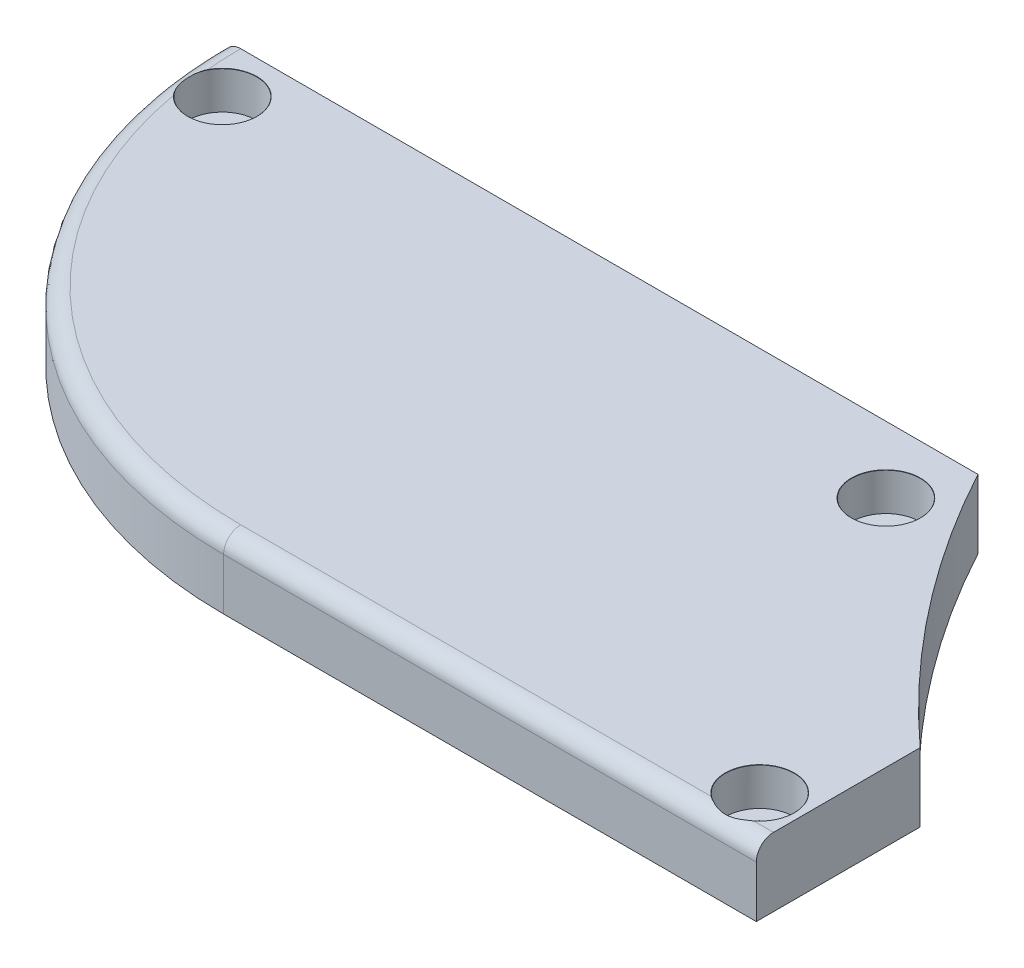
SolidWorks part; units mm, degrees
ref_plane "Front Plane" through (0, 0, 0) normal (0, 0, 1) x (1, 0, 0)
ref_plane "Top Plane" through (0, 0, 0) normal (0, 1, 0) x (1, 0, 0)
ref_plane "Right Plane" through (0, 0, 0) normal (1, 0, 0) x (0, 0, -1)
sketch "Sketch6" plane through (0, 0, 0) normal (0, 1, 0) x (1, 0, 0)
  line L2 (-49.2415, 24.8645) -> (-56.554, 24.8645)
  line L3 (-6.554, -25.1355) -> (55.4701, -25.1355)
  line L4 (55.4701, -25.1355) -> (55.4701, -6.0571)
  line L5 (31.2807, 24.8645) -> (15.2575, 24.8645)
  line L6 (-49.2415, 24.8645) -> (15.2575, 24.8645)
  arc A4 (-56.554, 24.8645) -> (-6.554, -25.1355) centre (-6.554, 24.8645) ccw
  arc A5 (31.2807, 24.8645) -> (55.4701, -6.0571) centre (133.446, 79.8645) ccw
extrude "Boss-Extrude2" add sketch "Sketch6" along normal blind 8 contours L6 L2 A4 L3 L4 A5 L5
sketch "Sketch7" plane through (0, 8, 0) normal (0, 1, 0) x (1, 0, 0)
  circle A0 centre (-52.2739, 21.307) radius 2.025
  circle A1 centre (50.689, -19.9544) radius 2.025
  circle A7 centre (28.2999, 17.1229) radius 2.025
sketch "Sketch11" plane through (0, 8, 0) normal (0, 1, 0) x (1, 0, 0)
  line L0 (50.4701, -8.2436) -> (50.4701, -18.1474)
  line L1 (48.0604, -20.1355) -> (-6.554, -20.1355)
  line L2 (-46.6352, 24.8645) -> (-56.554, 24.8645)
  line L3 (-6.554, -25.1355) -> (55.4701, -25.1355)
  line L4 (55.4701, -25.1355) -> (55.4701, -6.0571)
  line L5 (31.2807, 24.8645) -> (15.2575, 24.8645)
  circle A0 centre (-50.8096, 18.9764) radius 2.025
  arc A1 (48.0604, -20.1355) -> (50.4701, -18.1474) centre (50.0854, -20.1355) ccw
  arc A2 (-50.6388, 15.8351) -> (-6.554, -20.1355) centre (-6.554, 24.8645) ccw
  arc A3 (-56.554, 24.8645) -> (-6.554, -25.1355) centre (-6.554, 24.8645) ccw
  arc A4 (31.2807, 24.8645) -> (55.4701, -6.0571) centre (133.446, 79.8645) ccw
  arc A5 (31.9468, 13.9406) -> (50.4701, -8.2436) centre (133.446, 79.8645) ccw
  parabola Q0 (-50.6388, 15.8351) -> (-46.6352, 24.8645) focus (-49.7568, 20.4276) apex (-47.0818, 18.9898)
  spline S0 degree 3 poles (15.2575, 24.8645) (23.9964, 24.6371) (21.8005, 8.7848) (31.9468, 13.9406) knots 0 0 0 0 1 1 1 1
hole_wizard "CBORE for M4 Hex Socket Head Cap Screw1" positions "Sketch8" profile "Sketch9" counterbore size "M4" standard "ISO"
sketch "Sketch8" plane through (0, 8, 0) normal (0, 1, 0) x (1, 0, 0)
  point P3 (28.2999, 17.1229)
  point P6 (50.689, -19.9544)
  point P14 (-50.8096, 18.9764)
sketch "Sketch9" plane through (28.2999, 8, -17.1229) normal (1, 0, 0) x (0, 0, 1)
  line L0 (0, 0) -> (0, 11.4519)
  line L1 (0, 11.4519) -> (2.25, 10.1)
  line L2 (2.25, 10.1) -> (2.25, 4.4)
  line L3 (2.25, 4.4) -> (4, 4.4)
  line L5 (4, 4.4) -> (4, 0.025)
  line L6 (4, 0.025) -> (4.025, 0)
  line L7 (4.025, 0) -> (0, 0)
  line L8 (-4, 0.025) -> (-4.025, 0) construction
  line L10 (0, 11.4519) -> (-2.25, 10.1) construction
  line L11 (0, -6.35) -> (0, 107.95) construction
  dimension "Hole Dia." = 4.5
  dimension "Hole Depth" = 10.1
  dimension "C'Bore Dia." = 8
  dimension "C'Bore Depth" = 4.4
  dimension "Near C'Sink Dia." = 8.05
  dimension "Near C'Sink Angle" = 90
  dimension "Drill Angle" = 118
fillet "Fillet1" radius 2 2 edges at (24.458, 8, 25.1355) (-41.9094, 8, 10.4908)
